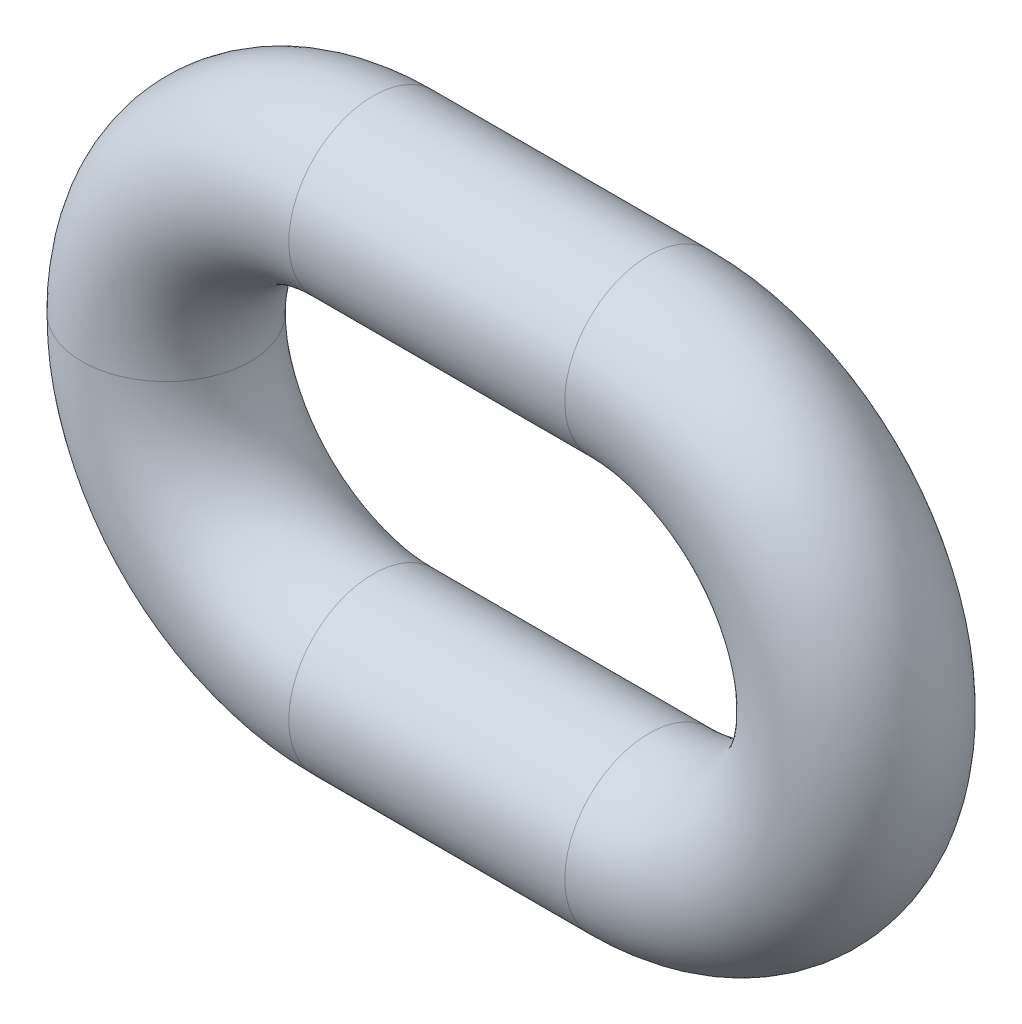
SolidWorks part; units mm, degrees
ref_plane "Front Plane" through (0, 0, 0) normal (0, 0, 1) x (1, 0, 0)
ref_plane "Top Plane" through (0, 0, 0) normal (0, 1, 0) x (1, 0, 0)
ref_plane "Right Plane" through (0, 0, 0) normal (1, 0, 0) x (0, 0, -1)
sketch "Sketch1" plane through (0, 0, 0) normal (0, 0, 1) x (1, 0, 0)
  line L0 (4.064, 0) -> (13.208, 0) construction
  line L1 (4.064, 4.064) -> (13.208, 4.064)
  line L2 (4.064, -4.064) -> (13.208, -4.064)
  arc A0 (4.064, 4.064) -> (4.064, -4.064) centre (4.064, 0) ccw
  arc A1 (13.208, -4.064) -> (13.208, 4.064) centre (13.208, 0) ccw
  point P3 (8.636, 0)
  point P8 (8.636, -4.064)
  point P11 (17.272, 0)
  dimension "LG" = 17.272
  dimension "WD" = 8.128
  dimension "PATTERNDIST" = 9.144
sketch "Sketch5" plane through (0, 0, 0) normal (0, 1, 0) x (1, 0, 0)
  circle A0 centre (-2.794, 0) radius 2.794
  dimension "THICK" = 5.588
sweep "Sweep1" add profiles "Sketch5" path "Sketch1"
ref_axis "Axis1" through (13.208, 0, 0) along (0, 0, 1)
ref_axis "Axis2" through (-2.794, 0, 0) along (0, 1, 0)
equation "\"PATTERNDISTANE\"= \"PATTERNDISTANCE\""
equation "\"LINKSPERFOOT\"= \"LINKS PER FOOT\""
